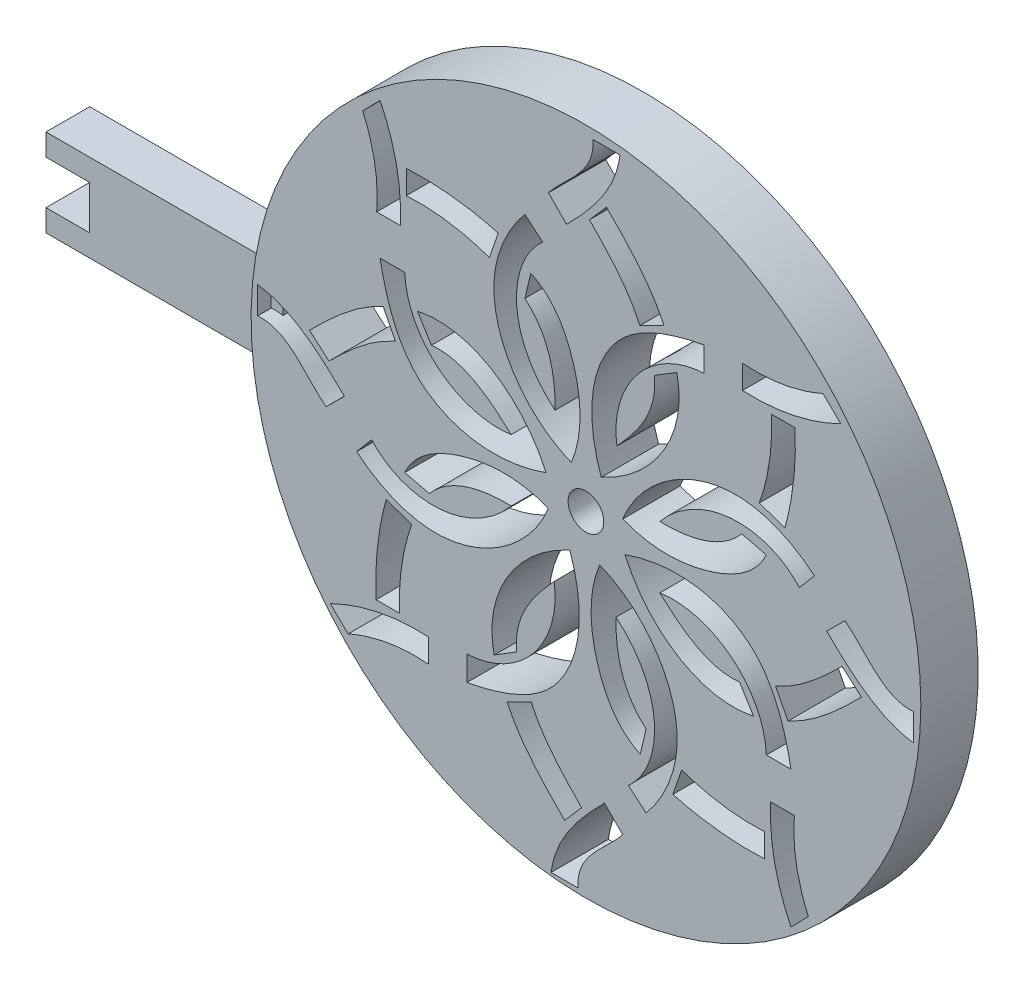
SolidWorks part; units mm, degrees
ref_plane "Front" through (0, 0, 0) normal (0, 0, 1) x (1, 0, 0)
ref_plane "Top" through (0, 0, 0) normal (0, 1, 0) x (1, 0, 0)
ref_plane "Right" through (0, 0, 0) normal (1, 0, 0) x (0, 0, -1)
sketch "Sketch4" plane through (0, 0, 0) normal (0, 0, 1) x (1, 0, 0)
  circle A0 centre (0, 0) radius 50
  dimension "D1" = 100
extrude "Boss-Extrude2" add sketch "Sketch4" along normal blind 6
sketch "Sketch1" plane through (0, 0, 0) normal (0, 0, 1) x (1, 0, 0)
  line L0 (0.5618, -51.3135) -> (0.5618, 17.3944) construction
  line L1 (-9.4536, -6.8886) -> (10.6305, 13.0689) construction
  line L2 (10.5773, -6.8886) -> (-9.5068, 13.0689) construction
  line L3 (16.331, 18.7335) -> (34.3707, 36.6595) construction
  line L4 (-9.5068, 13.0689) -> (-9.616, 13.1774) construction
  line L5 (6.3747, 16.0597) -> (8.2727, 17.2254)
  line L6 (10.5656, 20.3781) -> (10.5656, 18.3041)
  line L7 (0.9205, 24.6763) -> (2.3432, 26.3134)
  line L8 (5.1622, 19.0877) -> (7.1859, 20.1236)
  line L9 (4.5763, 24.9198) -> (5.8367, 23.184)
  line L11 (-12.0639, 21.0827) -> (-9.929, 21.0827)
  line L12 (-4.0159, 18.3041) -> (-4.513, 16.2283)
  line L13 (-4.513, 22.3493) -> (-3.0126, 21.0827)
  line L14 (-14.4893, 20.7159) -> (-14.4893, 18.7295)
  line L15 (-6.7607, 19.8672) -> (-7.5011, 17.7107)
  line L16 (-2.5302, 24.9198) -> (-1.0081, 23.3798)
  line L17 (1.2061, 30.6817) -> (3.4892, 30.6817)
  line L18 (-2.5302, 34.7098) -> (-0.6015, 34.7098)
  line L19 (-1.1362, 27.3587) -> (0.3144, 29.123)
  line L20 (13.7987, 20.6617) -> (13.7987, 18.6754)
  line L21 (20.5701, 21.8398) -> (22.067, 20.3781)
  line L22 (19.2048, 26.9759) -> (12.7252, 33.377)
  line L23 (17.8555, 25.6351) -> (12.2951, 31.1281)
  line L24 (12.7252, 33.377) -> (0.3144, 33.377)
  line L25 (0.3144, 33.377) -> (0.3144, 31.1281)
  line L26 (0.3144, 31.1281) -> (12.2951, 31.1281)
  line L27 (17.8555, 25.6351) -> (19.2048, 26.9759)
  line L28 (23.4061, 25.764) -> (14.5889, 34.4742)
  line L29 (14.5889, 34.4742) -> (17.3118, 40.6124)
  line L30 (15.254, 41.2328) -> (12.5727, 35.1885)
  line L31 (12.5727, 35.1885) -> (4.441, 35.1885)
  line L32 (4.441, 37.3216) -> (4.441, 35.1885)
  line L33 (4.441, 37.3216) -> (11.2937, 37.3216)
  line L34 (12.2009, 39.3665) -> (11.2937, 37.3216)
  line L35 (12.2009, 39.3665) -> (8.9373, 39.3665)
  line L36 (8.9373, 39.3665) -> (8.9373, 45.5487)
  line L37 (8.9373, 45.5487) -> (18.2458, 45.5487)
  line L38 (18.2458, 45.5487) -> (24.7099, 39.1361)
  line L39 (24.7099, 39.1361) -> (20.2368, 34.6271)
  line L40 (20.2368, 34.6271) -> (17.9282, 36.9173)
  line L41 (17.9282, 36.9173) -> (17.1172, 35.0891)
  line L42 (17.1172, 35.0891) -> (25.0916, 27.2115)
  line L43 (15.254, 41.2328) -> (11.0745, 41.2328)
  line L44 (11.0745, 41.2328) -> (11.0745, 43.6634)
  line L45 (11.0745, 43.6634) -> (17.6002, 43.6634)
  line L46 (17.6002, 43.6634) -> (21.9083, 39.2961)
  line L47 (21.9083, 39.2961) -> (20.2368, 37.6472)
  line L48 (20.2368, 37.6472) -> (17.3118, 40.6124)
  line L49 (20.5701, 27.611) -> (22.067, 26.3134)
  line L50 (16.4095, 21.4222) -> (18.768, 21.6675)
  line L51 (25.0916, 27.2115) -> (23.6255, 25.522)
  line L52 (23.6255, 25.522) -> (23.4061, 25.764)
  line L53 (26.0704, 37.6472) -> (21.7113, 33.377)
  line L54 (21.7113, 33.377) -> (24.0735, 30.9656)
  line L55 (24.0735, 30.9656) -> (22.8924, 29.8086)
  line L56 (22.8924, 29.8086) -> (24.3522, 28.3184)
  line L57 (24.3522, 28.3184) -> (26.9932, 30.9056)
  line L58 (26.9932, 30.9056) -> (24.7099, 33.2364)
  line L59 (24.7099, 33.2364) -> (26.2751, 34.7697)
  line L60 (26.2751, 34.7697) -> (32.3683, 28.6378)
  line L61 (32.3683, 28.6378) -> (30.7703, 27.0498)
  line L62 (30.7703, 27.0498) -> (28.3813, 29.454)
  line L63 (28.3813, 29.454) -> (23.1298, 24.2356)
  line L64 (23.1298, 24.2356) -> (24.575, 22.7369)
  line L65 (24.575, 22.7369) -> (28.5035, 26.525)
  line L66 (28.5035, 26.525) -> (30.5648, 24.3873)
  line L67 (30.5648, 24.3873) -> (35.1023, 28.7626)
  line L68 (35.1023, 28.7626) -> (26.0704, 37.6472)
  line L69 (-15.9935, 35.0891) -> (-20.9992, 30.1442)
  line L70 (-16.8045, 36.9173) -> (-15.9935, 35.0891)
  line L71 (-19.1132, 34.6271) -> (-16.8045, 36.9173)
  line L72 (-23.5862, 39.1361) -> (-19.1132, 34.6271)
  line L73 (-17.1221, 45.5487) -> (-23.5862, 39.1361)
  line L74 (-7.8136, 45.5487) -> (-17.1221, 45.5487)
  line L75 (-7.8136, 39.3665) -> (-7.8136, 45.5487)
  line L76 (-11.0772, 39.3665) -> (-7.8136, 39.3665)
  line L77 (-11.0772, 39.3665) -> (-10.17, 37.3216)
  line L78 (-3.3173, 37.3216) -> (-10.17, 37.3216)
  line L79 (-11.449, 35.1885) -> (-3.3173, 35.1885)
  line L80 (-14.1303, 41.2328) -> (-11.449, 35.1885)
  line L81 (-14.1303, 41.2328) -> (-9.9508, 41.2328)
  line L82 (-9.9508, 41.2328) -> (-9.9508, 43.6634)
  line L83 (-9.9508, 43.6634) -> (-16.4765, 43.6634)
  line L84 (-16.4765, 43.6634) -> (-20.7847, 39.2961)
  line L85 (-20.7847, 39.2961) -> (-19.1132, 37.6472)
  line L86 (-19.1132, 37.6472) -> (-16.1881, 40.6124)
  line L87 (-13.4652, 34.4742) -> (-16.1881, 40.6124)
  line L88 (-19.443, 28.5689) -> (-13.4652, 34.4742)
  line L89 (-19.443, 28.5689) -> (-20.9992, 30.1442)
  line L90 (-3.3173, 37.3216) -> (0.941, 37.3216)
  line L91 (0.941, 37.3216) -> (0.941, 35.0932)
  line L92 (0.941, 35.0932) -> (-3.3173, 35.1885)
  line L93 (-3.1732, 33.377) -> (-3.0126, 31.1281)
  line L94 (-3.0126, 31.1281) -> (-11.0772, 31.1281)
  line L95 (-11.0772, 31.1281) -> (-19.545, 22.5969)
  line L96 (-19.545, 22.5969) -> (-21.0309, 24.0717)
  line L97 (-21.0309, 24.0717) -> (-11.8349, 33.3366)
  line L98 (-11.8349, 33.3366) -> (-3.1732, 33.377)
  line L99 (1.441, 33.7567) -> (3.941, 33.7567)
  line L100 (3.941, 33.7567) -> (3.941, 39.3665)
  line L101 (3.941, 39.3665) -> (7.1859, 39.3665)
  line L102 (7.1859, 39.3665) -> (7.1859, 45.7803)
  line L103 (7.1859, 45.7803) -> (-5.8659, 45.7803)
  line L104 (-5.8659, 45.7803) -> (-5.8659, 39.3665)
  line L105 (-5.8659, 39.3665) -> (-2.5302, 39.3665)
  line L106 (-2.5302, 39.3665) -> (-2.5302, 37.8562)
  line L107 (-2.5302, 37.8562) -> (-0.6015, 37.8562)
  line L108 (-0.6015, 37.8562) -> (-0.6015, 41.6147)
  line L109 (-0.6015, 41.6147) -> (-3.5241, 41.6147)
  line L110 (-3.5241, 41.6147) -> (-3.5241, 43.6634)
  line L111 (-3.5241, 43.6634) -> (4.93, 43.6634)
  line L112 (4.93, 43.6634) -> (4.93, 41.6147)
  line L113 (4.93, 41.6147) -> (1.441, 41.6147)
  line L114 (1.441, 41.6147) -> (1.441, 33.7567)
  line L115 (39.1129, 2.2376) -> (31.255, 2.2376)
  line L116 (31.255, 2.2376) -> (31.255, -0.2624)
  line L117 (31.255, -0.2624) -> (36.8648, -0.2624)
  line L118 (36.8648, -0.2624) -> (36.8648, -3.5074)
  line L119 (36.8648, -3.5074) -> (43.2785, -3.5074)
  line L120 (43.2785, -3.5074) -> (43.2785, 9.5445)
  line L121 (43.2785, 9.5445) -> (36.8648, 9.5445)
  line L122 (36.8648, 9.5445) -> (36.8648, 6.2088)
  line L123 (36.8648, 6.2088) -> (35.3545, 6.2088)
  line L124 (35.3545, 6.2088) -> (35.3545, 4.28)
  line L125 (35.3545, 4.28) -> (39.1129, 4.28)
  line L126 (39.1129, 4.28) -> (39.1129, 7.2026)
  line L127 (39.1129, 7.2026) -> (41.1616, 7.2026)
  line L128 (41.1616, 7.2026) -> (41.1616, -1.2515)
  line L129 (41.1616, -1.2515) -> (39.1129, -1.2515)
  line L130 (39.1129, -1.2515) -> (39.1129, 2.2376)
  line L131 (23.0203, -19.9469) -> (23.2623, -19.7275)
  line L132 (23.2623, -19.7275) -> (31.9725, -10.9103)
  line L133 (31.9725, -10.9103) -> (38.1107, -13.6332)
  line L134 (35.1455, -16.5583) -> (38.1107, -13.6332)
  line L135 (36.7943, -18.2298) -> (35.1455, -16.5583)
  line L136 (41.1616, -13.9216) -> (36.7943, -18.2298)
  line L137 (41.1616, -7.3959) -> (41.1616, -13.9216)
  line L138 (38.731, -7.3959) -> (41.1616, -7.3959)
  line L139 (38.731, -11.5754) -> (38.731, -7.3959)
  line L140 (38.731, -11.5754) -> (32.6867, -8.8941)
  line L141 (32.6867, -8.8941) -> (32.6867, -0.7624)
  line L142 (34.8199, -0.7624) -> (32.6867, -0.7624)
  line L143 (34.8199, -0.7624) -> (34.8199, -7.6151)
  line L144 (36.8648, -8.5223) -> (34.8199, -7.6151)
  line L145 (36.8648, -8.5223) -> (36.8648, -5.2587)
  line L146 (36.8648, -5.2587) -> (43.047, -5.2587)
  line L147 (43.047, -5.2587) -> (43.047, -14.5672)
  line L148 (43.047, -14.5672) -> (36.6344, -21.0313)
  line L149 (36.6344, -21.0313) -> (32.1253, -16.5583)
  line L150 (32.1253, -16.5583) -> (34.4156, -14.2496)
  line L151 (34.4156, -14.2496) -> (32.5874, -13.4386)
  line L152 (32.5874, -13.4386) -> (24.7098, -21.413)
  line L153 (24.7098, -21.413) -> (23.0203, -19.9469)
  line L154 (26.2609, -31.4238) -> (35.1455, -22.3918)
  line L155 (35.1455, -22.3918) -> (30.8753, -18.0327)
  line L156 (30.8753, -18.0327) -> (28.4639, -20.395)
  line L157 (28.4639, -20.395) -> (27.3069, -19.2138)
  line L158 (27.3069, -19.2138) -> (25.8167, -20.6736)
  line L159 (25.8167, -20.6736) -> (28.4039, -23.3146)
  line L160 (28.4039, -23.3146) -> (30.7346, -21.0313)
  line L161 (30.7346, -21.0313) -> (32.2679, -22.5965)
  line L162 (32.2679, -22.5965) -> (26.1361, -28.6898)
  line L163 (26.1361, -28.6898) -> (24.5481, -27.0918)
  line L164 (24.5481, -27.0918) -> (26.9523, -24.7027)
  line L165 (26.9523, -24.7027) -> (21.7339, -19.4512)
  line L166 (21.7339, -19.4512) -> (20.2352, -20.8964)
  line L167 (20.2352, -20.8964) -> (24.0233, -24.8249)
  line L168 (24.0233, -24.8249) -> (21.8856, -26.8862)
  line L169 (21.8856, -26.8862) -> (26.2609, -31.4238)
  line L170 (32.5915, 2.7376) -> (32.6867, 6.9959)
  line L171 (32.6867, 15.1276) -> (32.6867, 6.9959)
  line L172 (38.731, 17.8089) -> (32.6867, 15.1276)
  line L173 (38.731, 17.8089) -> (38.731, 13.6294)
  line L174 (38.731, 13.6294) -> (41.1616, 13.6294)
  line L175 (41.1616, 13.6294) -> (41.1616, 20.1551)
  line L176 (41.1616, 20.1551) -> (36.7943, 24.4632)
  line L177 (36.7943, 24.4632) -> (35.1455, 22.7917)
  line L178 (35.1455, 22.7917) -> (38.1107, 19.8667)
  line L179 (31.9725, 17.1438) -> (38.1107, 19.8667)
  line L180 (26.0672, 23.1216) -> (31.9725, 17.1438)
  line L181 (26.0672, 23.1216) -> (27.6425, 24.6778)
  line L182 (32.5874, 19.6721) -> (27.6425, 24.6778)
  line L183 (34.4156, 20.4831) -> (32.5874, 19.6721)
  line L184 (32.1253, 22.7917) -> (34.4156, 20.4831)
  line L185 (36.6344, 27.2648) -> (32.1253, 22.7917)
  line L186 (43.047, 20.8007) -> (36.6344, 27.2648)
  line L187 (43.047, 11.4922) -> (43.047, 20.8007)
  line L188 (36.8648, 11.4922) -> (43.047, 11.4922)
  line L189 (36.8648, 14.7558) -> (36.8648, 11.4922)
  line L190 (36.8648, 14.7558) -> (34.8199, 13.8486)
  line L191 (34.8199, 6.9959) -> (34.8199, 13.8486)
  line L192 (34.8199, 6.9959) -> (34.8199, 2.7376)
  line L193 (34.8199, 2.7376) -> (32.5915, 2.7376)
  line L194 (23.1334, -14.177) -> (24.4742, -15.5263)
  line L195 (24.4742, -15.5263) -> (30.8753, -9.0466)
  line L196 (30.8753, -9.0466) -> (30.8753, 3.3641)
  line L197 (30.8753, 3.3641) -> (28.6264, 3.3641)
  line L198 (28.6264, 3.3641) -> (28.6264, -8.6165)
  line L199 (23.1334, -14.177) -> (28.6264, -8.6165)
  line L200 (30.8348, 15.5135) -> (30.8753, 6.8518)
  line L201 (30.8753, 6.8518) -> (28.6264, 6.6912)
  line L202 (28.6264, 6.6912) -> (28.6264, 14.7558)
  line L203 (28.6264, 14.7558) -> (20.0952, 23.2236)
  line L204 (20.0952, 23.2236) -> (21.57, 24.7094)
  line L205 (21.57, 24.7094) -> (30.8348, 15.5135)
  line L206 (18.9205, -12.7309) -> (19.1658, -15.0894)
  line L207 (25.1092, -16.8915) -> (23.8117, -18.3884)
  line L208 (24.857, 4.8148) -> (26.6212, 3.3641)
  line L209 (32.2081, 6.2088) -> (32.2081, 4.28)
  line L210 (28.18, 2.4725) -> (28.18, 0.1894)
  line L211 (22.4181, 6.2088) -> (20.8781, 4.6867)
  line L212 (22.4181, -0.8977) -> (20.6823, -2.1581)
  line L213 (16.586, -1.4836) -> (17.6218, -3.5074)
  line L214 (22.1746, 2.7581) -> (23.8117, 1.3354)
  line L215 (19.3381, -16.8915) -> (17.8764, -18.3884)
  line L216 (18.16, -10.1201) -> (16.1736, -10.1201)
  line L217 (17.3654, 10.4393) -> (15.209, 11.1797)
  line L218 (18.2141, 18.1679) -> (16.2278, 18.1679)
  line L219 (19.8476, 8.1916) -> (18.581, 6.6912)
  line L220 (15.8023, 7.6945) -> (13.7266, 8.1916)
  line L221 (17.8764, -6.887) -> (15.8023, -6.887)
  line L222 (13.558, -2.6961) -> (14.7236, -4.5941)
  line L223 (20.0952, 1.5374) -> (18.581, 0.1894)
  line L224 (18.581, 15.7425) -> (18.581, 13.6075)
  line L225 (-0.2642, -35.4343) -> (-0.2642, -27.5764)
  line L226 (-0.2642, -27.5764) -> (-2.7642, -27.5764)
  line L227 (-2.7642, -27.5764) -> (-2.7642, -33.1862)
  line L228 (-2.7642, -33.1862) -> (-6.0091, -33.1862)
  line L229 (-6.0091, -33.1862) -> (-6.0091, -39.6)
  line L230 (-6.0091, -39.6) -> (7.0427, -39.6)
  line L231 (7.0427, -39.6) -> (7.0427, -33.1862)
  line L232 (7.0427, -33.1862) -> (3.707, -33.1862)
  line L233 (3.707, -33.1862) -> (3.707, -31.6759)
  line L234 (3.707, -31.6759) -> (1.7783, -31.6759)
  line L235 (1.7783, -31.6759) -> (1.7783, -35.4343)
  line L236 (1.7783, -35.4343) -> (4.7009, -35.4343)
  line L237 (4.7009, -35.4343) -> (4.7009, -37.4831)
  line L238 (4.7009, -37.4831) -> (-3.7532, -37.4831)
  line L239 (-3.7532, -37.4831) -> (-3.7532, -35.4343)
  line L240 (-3.7532, -35.4343) -> (-0.2642, -35.4343)
  line L241 (-22.4487, -19.3417) -> (-22.2292, -19.5837)
  line L242 (-22.2292, -19.5837) -> (-13.412, -28.2939)
  line L243 (-13.412, -28.2939) -> (-16.135, -34.4321)
  line L244 (-19.06, -31.4669) -> (-16.135, -34.4321)
  line L245 (-20.7315, -33.1158) -> (-19.06, -31.4669)
  line L246 (-16.4233, -37.4831) -> (-20.7315, -33.1158)
  line L247 (-9.8976, -37.4831) -> (-16.4233, -37.4831)
  line L248 (-9.8976, -35.0525) -> (-9.8976, -37.4831)
  line L249 (-14.0771, -35.0525) -> (-9.8976, -35.0525)
  line L250 (-14.0771, -35.0525) -> (-11.3959, -29.0082)
  line L251 (-11.3959, -29.0082) -> (-3.2642, -29.0082)
  line L252 (-3.2642, -31.1413) -> (-3.2642, -29.0082)
  line L253 (-3.2642, -31.1413) -> (-10.1169, -31.1413)
  line L254 (-11.024, -33.1862) -> (-10.1169, -31.1413)
  line L255 (-11.024, -33.1862) -> (-7.7604, -33.1862)
  line L256 (-7.7604, -33.1862) -> (-7.7604, -39.3684)
  line L257 (-7.7604, -39.3684) -> (-17.0689, -39.3684)
  line L258 (-17.0689, -39.3684) -> (-23.5331, -32.9558)
  line L259 (-23.5331, -32.9558) -> (-19.06, -28.4468)
  line L260 (-19.06, -28.4468) -> (-16.7514, -30.737)
  line L261 (-16.7514, -30.737) -> (-15.9404, -28.9088)
  line L262 (-15.9404, -28.9088) -> (-23.9147, -21.0312)
  line L263 (-23.9147, -21.0312) -> (-22.4487, -19.3417)
  line L264 (-33.9255, -22.5823) -> (-24.8935, -31.4669)
  line L265 (-24.8935, -31.4669) -> (-20.5345, -27.1967)
  line L266 (-20.5345, -27.1967) -> (-22.8967, -24.7853)
  line L267 (-22.8967, -24.7853) -> (-21.7156, -23.6283)
  line L268 (-21.7156, -23.6283) -> (-23.1754, -22.1381)
  line L269 (-23.1754, -22.1381) -> (-25.8163, -24.7253)
  line L270 (-25.8163, -24.7253) -> (-23.5331, -27.0561)
  line L271 (-23.5331, -27.0561) -> (-25.0983, -28.5894)
  line L272 (-25.0983, -28.5894) -> (-31.1915, -22.4575)
  line L273 (-31.1915, -22.4575) -> (-29.5935, -20.8695)
  line L274 (-29.5935, -20.8695) -> (-27.2044, -23.2737)
  line L275 (-27.2044, -23.2737) -> (-21.9529, -18.0553)
  line L276 (-21.9529, -18.0553) -> (-23.3981, -16.5566)
  line L277 (-23.3981, -16.5566) -> (-27.3267, -20.3447)
  line L278 (-27.3267, -20.3447) -> (-29.388, -18.207)
  line L279 (-29.388, -18.207) -> (-33.9255, -22.5823)
  line L280 (0.2358, -28.9129) -> (4.4942, -29.0082)
  line L281 (12.6259, -29.0082) -> (4.4942, -29.0082)
  line L282 (15.3072, -35.0525) -> (12.6259, -29.0082)
  line L283 (15.3072, -35.0525) -> (11.1277, -35.0525)
  line L284 (11.1277, -35.0525) -> (11.1277, -37.4831)
  line L285 (11.1277, -37.4831) -> (17.6534, -37.4831)
  line L286 (17.6534, -37.4831) -> (21.9615, -33.1158)
  line L287 (21.9615, -33.1158) -> (20.29, -31.4669)
  line L288 (20.29, -31.4669) -> (17.365, -34.4321)
  line L289 (14.6421, -28.2939) -> (17.365, -34.4321)
  line L290 (20.6199, -22.3886) -> (14.6421, -28.2939)
  line L291 (20.6199, -22.3886) -> (22.176, -23.9639)
  line L292 (17.1704, -28.9088) -> (22.176, -23.9639)
  line L293 (17.9814, -30.737) -> (17.1704, -28.9088)
  line L294 (20.29, -28.4468) -> (17.9814, -30.737)
  line L295 (24.7631, -32.9558) -> (20.29, -28.4468)
  line L296 (18.2989, -39.3684) -> (24.7631, -32.9558)
  line L297 (8.9905, -39.3684) -> (18.2989, -39.3684)
  line L298 (8.9905, -33.1862) -> (8.9905, -39.3684)
  line L299 (12.2541, -33.1862) -> (8.9905, -33.1862)
  line L300 (12.2541, -33.1862) -> (11.3469, -31.1413)
  line L301 (4.4942, -31.1413) -> (11.3469, -31.1413)
  line L302 (4.4942, -31.1413) -> (0.2358, -31.1413)
  line L303 (0.2358, -31.1413) -> (0.2358, -28.9129)
  line L304 (-16.6787, -19.4548) -> (-18.028, -20.7956)
  line L305 (-18.028, -20.7956) -> (-11.5483, -27.1967)
  line L306 (-11.5483, -27.1967) -> (0.8624, -27.1967)
  line L307 (0.8624, -27.1967) -> (0.8624, -24.9478)
  line L308 (0.8624, -24.9478) -> (-11.1183, -24.9478)
  line L309 (-16.6787, -19.4548) -> (-11.1183, -24.9478)
  line L310 (13.0117, -27.1563) -> (4.3501, -27.1967)
  line L311 (4.3501, -27.1967) -> (4.1895, -24.9478)
  line L312 (4.1895, -24.9478) -> (12.2541, -24.9478)
  line L313 (12.2541, -24.9478) -> (20.7219, -16.4166)
  line L314 (20.7219, -16.4166) -> (22.2077, -17.8914)
  line L315 (22.2077, -17.8914) -> (13.0117, -27.1563)
  line L316 (-15.2326, -15.2419) -> (-17.5912, -15.4872)
  line L317 (-19.3933, -21.4307) -> (-20.8901, -20.1331)
  line L318 (2.313, -21.1784) -> (0.8624, -22.9427)
  line L319 (3.707, -28.5295) -> (1.7783, -28.5295)
  line L320 (-0.0293, -24.5014) -> (-2.3123, -24.5014)
  line L321 (3.707, -18.7395) -> (2.1849, -17.1995)
  line L322 (-3.3995, -18.7395) -> (-4.6598, -17.0037)
  line L323 (-3.9854, -12.9074) -> (-6.0091, -13.9433)
  line L324 (0.2564, -18.496) -> (-1.1663, -20.1331)
  line L325 (-19.3933, -15.6595) -> (-20.8901, -14.1978)
  line L326 (-12.6218, -14.4814) -> (-12.6218, -12.4951)
  line L327 (7.9376, -13.6868) -> (8.6779, -11.5304)
  line L328 (15.6662, -14.5355) -> (15.6662, -12.5492)
  line L329 (5.6899, -16.169) -> (4.1895, -14.9024)
  line L330 (5.1928, -12.1238) -> (5.6899, -10.048)
  line L331 (-9.3887, -14.1978) -> (-9.3887, -12.1238)
  line L332 (-5.1978, -9.8794) -> (-7.0958, -11.0451)
  line L333 (-0.9643, -16.4166) -> (-2.3123, -14.9024)
  line L334 (13.2408, -14.9024) -> (11.1058, -14.9024)
  line L335 (-37.9361, 3.9427) -> (-30.0781, 3.9427)
  line L336 (-30.0781, 3.9427) -> (-30.0781, 6.4427)
  line L337 (-30.0781, 6.4427) -> (-35.688, 6.4427)
  line L338 (-35.688, 6.4427) -> (-35.688, 9.6877)
  line L339 (-35.688, 9.6877) -> (-42.1017, 9.6877)
  line L340 (-42.1017, 9.6877) -> (-42.1017, -3.3642)
  line L341 (-42.1017, -3.3642) -> (-35.688, -3.3642)
  line L342 (-35.688, -3.3642) -> (-35.688, -0.0285)
  line L343 (-35.688, -0.0285) -> (-34.1776, -0.0285)
  line L344 (-34.1776, -0.0285) -> (-34.1776, 1.9003)
  line L345 (-34.1776, 1.9003) -> (-37.9361, 1.9003)
  line L346 (-37.9361, 1.9003) -> (-37.9361, -1.0223)
  line L347 (-37.9361, -1.0223) -> (-39.9848, -1.0223)
  line L348 (-39.9848, -1.0223) -> (-39.9848, 7.4318)
  line L349 (-39.9848, 7.4318) -> (-37.9361, 7.4318)
  line L350 (-37.9361, 7.4318) -> (-37.9361, 3.9427)
  line L351 (-21.8435, 26.1272) -> (-22.0854, 25.9078)
  line L352 (-22.0854, 25.9078) -> (-30.7956, 17.0906)
  line L353 (-30.7956, 17.0906) -> (-36.9338, 19.8135)
  line L354 (-33.9686, 22.7386) -> (-36.9338, 19.8135)
  line L355 (-35.6175, 24.4101) -> (-33.9686, 22.7386)
  line L356 (-39.9848, 20.1019) -> (-35.6175, 24.4101)
  line L357 (-39.9848, 13.5762) -> (-39.9848, 20.1019)
  line L358 (-37.5542, 13.5762) -> (-39.9848, 13.5762)
  line L359 (-37.5542, 17.7557) -> (-37.5542, 13.5762)
  line L360 (-37.5542, 17.7557) -> (-31.5099, 15.0744)
  line L361 (-31.5099, 15.0744) -> (-31.5099, 6.9427)
  line L362 (-33.643, 6.9427) -> (-31.5099, 6.9427)
  line L363 (-33.643, 6.9427) -> (-33.643, 13.7954)
  line L364 (-35.688, 14.7026) -> (-33.643, 13.7954)
  line L365 (-35.688, 14.7026) -> (-35.688, 11.439)
  line L366 (-35.688, 11.439) -> (-41.8701, 11.439)
  line L367 (-41.8701, 11.439) -> (-41.8701, 20.7475)
  line L368 (-41.8701, 20.7475) -> (-35.4575, 27.2116)
  line L369 (-35.4575, 27.2116) -> (-30.9485, 22.7386)
  line L370 (-30.9485, 22.7386) -> (-33.2387, 20.4299)
  line L371 (-33.2387, 20.4299) -> (-31.4105, 19.6189)
  line L372 (-31.4105, 19.6189) -> (-23.5329, 27.5933)
  line L373 (-23.5329, 27.5933) -> (-21.8435, 26.1272)
  line L374 (-25.084, 37.6041) -> (-33.9686, 28.5721)
  line L375 (-33.9686, 28.5721) -> (-29.6984, 24.213)
  line L376 (-29.6984, 24.213) -> (-27.2871, 26.5753)
  line L377 (-27.2871, 26.5753) -> (-26.13, 25.3941)
  line L378 (-26.13, 25.3941) -> (-24.6399, 26.8539)
  line L379 (-24.6399, 26.8539) -> (-27.227, 29.4949)
  line L380 (-27.227, 29.4949) -> (-29.5578, 27.2116)
  line L381 (-29.5578, 27.2116) -> (-31.0911, 28.7768)
  line L382 (-31.0911, 28.7768) -> (-24.9592, 34.8701)
  line L383 (-24.9592, 34.8701) -> (-23.3713, 33.2721)
  line L384 (-23.3713, 33.2721) -> (-25.7755, 30.883)
  line L385 (-25.7755, 30.883) -> (-20.5571, 25.6315)
  line L386 (-20.5571, 25.6315) -> (-19.0583, 27.0767)
  line L387 (-19.0583, 27.0767) -> (-22.8464, 31.0053)
  line L388 (-22.8464, 31.0053) -> (-20.7087, 33.0665)
  line L389 (-20.7087, 33.0665) -> (-25.084, 37.6041)
  line L390 (-31.4146, 3.4427) -> (-31.5099, -0.8156)
  line L391 (-31.5099, -8.9473) -> (-31.5099, -0.8156)
  line L392 (-37.5542, -11.6286) -> (-31.5099, -8.9473)
  line L393 (-37.5542, -11.6286) -> (-37.5542, -7.4491)
  line L394 (-37.5542, -7.4491) -> (-39.9848, -7.4491)
  line L395 (-39.9848, -7.4491) -> (-39.9848, -13.9748)
  line L396 (-39.9848, -13.9748) -> (-35.6175, -18.2829)
  line L397 (-35.6175, -18.2829) -> (-33.9686, -16.6114)
  line L398 (-33.9686, -16.6114) -> (-36.9338, -13.6864)
  line L399 (-30.7956, -10.9635) -> (-36.9338, -13.6864)
  line L400 (-24.8903, -16.9413) -> (-30.7956, -10.9635)
  line L401 (-24.8903, -16.9413) -> (-26.4656, -18.4975)
  line L402 (-31.4105, -13.4918) -> (-26.4656, -18.4975)
  line L403 (-33.2387, -14.3028) -> (-31.4105, -13.4918)
  line L404 (-30.9485, -16.6114) -> (-33.2387, -14.3028)
  line L405 (-35.4575, -21.0845) -> (-30.9485, -16.6114)
  line L406 (-41.8701, -14.6204) -> (-35.4575, -21.0845)
  line L407 (-41.8701, -5.3119) -> (-41.8701, -14.6204)
  line L408 (-35.688, -5.3119) -> (-41.8701, -5.3119)
  line L409 (-35.688, -8.5755) -> (-35.688, -5.3119)
  line L410 (-35.688, -8.5755) -> (-33.643, -7.6683)
  line L411 (-33.643, -0.8156) -> (-33.643, -7.6683)
  line L412 (-33.643, -0.8156) -> (-33.643, 3.4427)
  line L413 (-33.643, 3.4427) -> (-31.4146, 3.4427)
  line L414 (-21.9566, 20.3573) -> (-23.2973, 21.7066)
  line L415 (-23.2973, 21.7066) -> (-29.6984, 15.2269)
  line L416 (-29.6984, 15.2269) -> (-29.6984, 2.8162)
  line L417 (-29.6984, 2.8162) -> (-27.4496, 2.8162)
  line L418 (-27.4496, 2.8162) -> (-27.4496, 14.7968)
  line L419 (-21.9566, 20.3573) -> (-27.4496, 14.7968)
  line L420 (-29.658, -9.3332) -> (-29.6984, -0.6715)
  line L421 (-29.6984, -0.6715) -> (-27.4496, -0.5109)
  line L422 (-27.4496, -0.5109) -> (-27.4496, -8.5755)
  line L423 (-27.4496, -8.5755) -> (-18.9184, -17.0433)
  line L424 (-18.9184, -17.0433) -> (-20.3932, -18.5291)
  line L425 (-20.3932, -18.5291) -> (-29.658, -9.3332)
  line L426 (-17.7436, 18.9112) -> (-17.9889, 21.2697)
  line L427 (-23.9324, 23.0718) -> (-22.6348, 24.5687)
  line L428 (-23.6801, 1.3655) -> (-25.4444, 2.8162)
  line L429 (-31.0312, -0.0285) -> (-31.0312, 1.9003)
  line L430 (-27.0032, 3.7078) -> (-27.0032, 5.9909)
  line L431 (-21.2412, -0.0285) -> (-19.7012, 1.4936)
  line L432 (-21.2412, 7.078) -> (-19.5054, 8.3384)
  line L433 (-15.4092, 7.6639) -> (-16.445, 9.6877)
  line L434 (-20.9977, 3.4222) -> (-22.6348, 4.8449)
  line L435 (-18.1612, 23.0718) -> (-16.6995, 24.5687)
  line L436 (-16.9831, 16.3004) -> (-14.9968, 16.3004)
  line L437 (-16.1886, -4.259) -> (-14.0322, -4.9994)
  line L438 (-17.0373, -11.9876) -> (-15.051, -11.9876)
  line L439 (-18.6707, -2.0113) -> (-17.4041, -0.5109)
  line L440 (-14.6255, -1.5142) -> (-12.5497, -2.0113)
  line L441 (-16.6995, 13.0673) -> (-14.6255, 13.0673)
  line L442 (-12.3811, 8.8764) -> (-13.5468, 10.7744)
  line L443 (-18.9184, 4.6429) -> (-17.4041, 5.9909)
  line L444 (-17.4041, -9.5622) -> (-17.4041, -7.4272)
  line L445 (-15.0302, 18.5575) -> (-34.8365, 38.2389) construction
  line L446 (0.5618, 25.0422) -> (0.5618, 52.6865) construction
  spline S0 degree 3 poles (1.9128, 6.4081) (5.9565, 8.1949) (9.2924, 12.4957) (8.2727, 17.2254) knots 0 0 0 0 1 1 1 1
  spline S1 degree 3 poles (1.9128, 6.4081) (1.0549, 8.7838) (0.6747, 12.8499) (3.9435, 18.6992) (8.1058, 19.9135) (10.5656, 20.3781) knots 0 0 0 0 0.397628 0.593751 1 1 1 1
  spline S2 degree 3 poles (10.5656, 18.3041) (8.5021, 18.2289) (4.3462, 16.0974) (2.887, 11.6127) (3.2274, 9.3434) knots 0 0 0 0 0.475044 1 1 1 1
  spline S3 degree 3 poles (3.2274, 9.3434) (4.909, 11.1573) (6.6886, 13.3688) (6.3747, 16.0597) knots 0 0 0 0 1 1 1 1
  spline S8 degree 3 poles (7.1859, 20.1236) (6.0615, 22.5345) (4.2017, 24.4648) (2.3432, 26.3134) knots 0 0 0 0 1 1 1 1
  spline S9 degree 3 poles (5.1622, 19.0877) (4.204, 21.2611) (2.5611, 23.0083) (0.9205, 24.6763) knots 0 0 0 0 1 1 1 1
  spline S16 degree 3 poles (-0.6015, 6.2318) (0.3774, 8.5914) (0.2368, 13.2339) (-2.0951, 17.4295) (-4.0159, 18.3041) knots 0 0 0 0 0.551732 1 1 1 1
  spline S17 degree 3 poles (-4.513, 16.2283) (-2.5157, 14.566) (-1.8872, 11.8216) (-1.9798, 9.3434) knots 0 0 0 0 1 1 1 1
  spline S18 degree 3 poles (-1.9798, 9.3434) (-3.3571, 10.4816) (-6.0015, 14.3076) (-5.1059, 19.2239) (-3.0126, 21.0827) knots 0 0 0 0 0.406587 1 1 1 1
  spline S19 degree 3 poles (-4.513, 22.3493) (-5.9818, 20.6238) (-8.8778, 14.3072) (-4.4607, 7.7513) (-0.6015, 6.2318) knots 0 0 0 0 0.358842 1 1 1 1
  spline S20 degree 2 poles (-14.4893, 20.7159) (-10.5651, 20.9108) (-6.7607, 19.8672) knots 0 0 0 1 1 1
  spline S21 degree 2 poles (-14.4893, 18.7295) (-10.9112, 18.9185) (-7.5011, 17.7107) knots 0 0 0 1 1 1
  spline S22 degree 3 poles (-1.0081, 23.3798) (0.9762, 25.3708) (3.1191, 27.7529) (3.4892, 30.6817) knots 0 0 0 0 1 1 1 1
  spline S23 degree 3 poles (1.2061, 30.6817) (1.4387, 28.1115) (-1.2075, 26.6689) (-2.5302, 24.9198) knots 0 0 0 0 1 1 1 1
  spline S24 degree 2 poles (-0.6015, 34.7098) (-1.0842, 31.7413) (0.3144, 29.123) knots 0 0 0 1 1 1
  spline S25 degree 2 poles (-2.5302, 34.7098) (-3.2008, 30.7791) (-1.1362, 27.3587) knots 0 0 0 1 1 1
  spline S26 degree 2 poles (13.7987, 20.6617) (17.3177, 20.3883) (20.5701, 21.8398) knots 0 0 0 1 1 1
  spline S27 degree 2 poles (13.7987, 18.6754) (18.1381, 18.4571) (22.067, 20.3781) knots 0 0 0 1 1 1
  spline S28 degree 3 poles (16.4095, 21.4222) (16.749, 24.0357) (18.841, 25.8563) (20.5701, 27.611) knots 0 0 0 0 1 1 1 1
  spline S29 degree 3 poles (18.768, 21.6675) (18.7945, 23.757) (20.731, 24.9709) (22.067, 26.3134) knots 0 0 0 0 1 1 1 1
  spline S32 degree 2 poles (15.4515, 15.8331) (15.4515, 14.9513) (15.4515, 14.0695) knots 0 0 0 1 1 1
  spline S33 degree 3 poles (19.1658, -15.0894) (21.2553, -15.1159) (22.4692, -17.0524) (23.8117, -18.3884) knots 0 0 0 0 1 1 1 1
  spline S34 degree 3 poles (18.9205, -12.7309) (21.534, -13.0704) (23.3546, -15.1625) (25.1092, -16.8915) knots 0 0 0 0 1 1 1 1
  spline S35 degree 2 poles (32.2081, 4.28) (29.2396, 4.7628) (26.6212, 3.3641) knots 0 0 0 1 1 1
  spline S36 degree 2 poles (32.2081, 6.2088) (28.2774, 6.8794) (24.857, 4.8148) knots 0 0 0 1 1 1
  spline S37 degree 3 poles (20.8781, 4.6867) (22.8691, 2.7024) (25.2512, 0.5595) (28.18, 0.1894) knots 0 0 0 0 1 1 1 1
  spline S38 degree 3 poles (28.18, 2.4725) (25.6097, 2.2399) (24.1672, 4.8861) (22.4181, 6.2088) knots 0 0 0 0 1 1 1 1
  spline S39 degree 2 poles (13.3314, -11.7729) (12.4496, -11.7729) (11.5678, -11.7729) knots 0 0 0 1 1 1
  spline S42 degree 2 poles (20.6823, -2.1581) (22.3603, -3.9755) (23.2727, -6.3014) knots 0 0 0 1 1 1
  spline S43 degree 3 poles (22.4181, -0.8977) (24.215, -2.6753) (24.9751, -5.1383) (25.9383, -7.3959) knots 0 0 0 0 1 1 1 1
  spline S46 degree 3 poles (17.6218, -3.5074) (20.0327, -2.3829) (21.9631, -0.5231) (23.8117, 1.3354) knots 0 0 0 0 1 1 1 1
  spline S47 degree 3 poles (16.586, -1.4836) (18.7594, -0.5255) (20.5066, 1.1175) (22.1746, 2.7581) knots 0 0 0 0 1 1 1 1
  spline S48 degree 2 poles (16.1736, -10.1201) (15.9553, -14.4595) (17.8764, -18.3884) knots 0 0 0 1 1 1
  spline S49 degree 2 poles (18.16, -10.1201) (17.8866, -13.6391) (19.3381, -16.8915) knots 0 0 0 1 1 1
  spline S50 degree 2 poles (16.2278, 18.1679) (16.4168, 14.5898) (15.209, 11.1797) knots 0 0 0 1 1 1
  spline S51 degree 2 poles (18.2141, 18.1679) (18.4091, 14.2437) (17.3654, 10.4393) knots 0 0 0 1 1 1
  spline S52 degree 3 poles (6.8417, 5.6584) (7.9799, 7.0357) (11.8059, 9.6801) (16.7222, 8.7845) (18.581, 6.6912) knots 0 0 0 0 0.406587 1 1 1 1
  spline S53 degree 3 poles (13.7266, 8.1916) (12.0643, 6.1943) (9.3199, 5.5658) (6.8417, 5.6584) knots 0 0 0 0 1 1 1 1
  spline S54 degree 3 poles (3.7301, 4.28) (6.0897, 3.3012) (10.7321, 3.4417) (14.9278, 5.7737) (15.8023, 7.6945) knots 0 0 0 0 0.551732 1 1 1 1
  spline S55 degree 3 poles (19.8476, 8.1916) (18.1221, 9.6604) (11.8055, 12.5564) (5.2495, 8.1393) (3.7301, 4.28) knots 0 0 0 0 0.358842 1 1 1 1
  spline S56 degree 3 poles (15.8023, -6.887) (15.7272, -4.8235) (13.5956, -0.6677) (9.111, 0.7916) (6.8417, 0.4512) knots 0 0 0 0 0.475044 1 1 1 1
  spline S57 degree 3 poles (6.8417, 0.4512) (8.6556, -1.2305) (10.8671, -3.0101) (13.558, -2.6961) knots 0 0 0 0 1 1 1 1
  spline S58 degree 3 poles (3.9064, 1.7658) (5.6932, -2.2779) (9.9939, -5.6138) (14.7236, -4.5941) knots 0 0 0 0 1 1 1 1
  spline S59 degree 3 poles (3.9064, 1.7658) (6.2821, 2.6237) (10.3482, 3.0039) (16.1975, -0.2649) (17.4118, -4.4272) (17.8764, -6.887) knots 0 0 0 0 0.397628 0.593751 1 1 1 1
  spline S66 degree 3 poles (-17.5912, -15.4872) (-17.6177, -17.5767) (-19.5542, -18.7906) (-20.8901, -20.1331) knots 0 0 0 0 1 1 1 1
  spline S67 degree 3 poles (-15.2326, -15.2419) (-15.5721, -17.8554) (-17.6642, -19.676) (-19.3933, -21.4307) knots 0 0 0 0 1 1 1 1
  spline S68 degree 2 poles (1.7783, -28.5295) (2.2611, -25.561) (0.8624, -22.9427) knots 0 0 0 1 1 1
  spline S69 degree 2 poles (3.707, -28.5295) (4.3777, -24.5988) (2.313, -21.1784) knots 0 0 0 1 1 1
  spline S70 degree 3 poles (2.1849, -17.1995) (0.2007, -19.1905) (-1.9422, -21.5726) (-2.3123, -24.5014) knots 0 0 0 0 1 1 1 1
  spline S71 degree 3 poles (-0.0293, -24.5014) (-0.2619, -21.9312) (2.3843, -20.4886) (3.707, -18.7395) knots 0 0 0 0 1 1 1 1
  spline S75 degree 2 poles (-4.6598, -17.0037) (-6.4772, -18.6818) (-8.8031, -19.5941) knots 0 0 0 1 1 1
  spline S76 degree 3 poles (-3.3995, -18.7395) (-5.177, -20.5365) (-7.64, -21.2965) (-9.8976, -22.2597) knots 0 0 0 0 1 1 1 1
  spline S79 degree 3 poles (-6.0091, -13.9433) (-4.8847, -16.3542) (-3.0248, -18.2845) (-1.1663, -20.1331) knots 0 0 0 0 1 1 1 1
  spline S80 degree 3 poles (-3.9854, -12.9074) (-3.0272, -15.0808) (-1.3842, -16.828) (0.2564, -18.496) knots 0 0 0 0 1 1 1 1
  spline S81 degree 2 poles (-12.6218, -12.4951) (-16.9612, -12.2768) (-20.8901, -14.1978) knots 0 0 0 1 1 1
  spline S82 degree 2 poles (-12.6218, -14.4814) (-16.1408, -14.208) (-19.3933, -15.6595) knots 0 0 0 1 1 1
  spline S83 degree 2 poles (15.6662, -12.5492) (12.0881, -12.7382) (8.6779, -11.5304) knots 0 0 0 1 1 1
  spline S84 degree 2 poles (15.6662, -14.5355) (11.742, -14.7305) (7.9376, -13.6868) knots 0 0 0 1 1 1
  spline S85 degree 3 poles (3.1567, -3.1631) (4.5339, -4.3013) (7.1784, -8.1273) (6.2827, -13.0436) (4.1895, -14.9024) knots 0 0 0 0 0.406587 1 1 1 1
  spline S86 degree 3 poles (5.6899, -10.048) (3.6926, -8.3857) (3.0641, -5.6413) (3.1567, -3.1631) knots 0 0 0 0 1 1 1 1
  spline S87 degree 3 poles (1.7783, -0.0515) (0.7995, -2.4111) (0.94, -7.0536) (3.2719, -11.2492) (5.1928, -12.1238) knots 0 0 0 0 0.551732 1 1 1 1
  spline S88 degree 3 poles (5.6899, -16.169) (7.1586, -14.4435) (10.0547, -8.1269) (5.6376, -1.5709) (1.7783, -0.0515) knots 0 0 0 0 0.358842 1 1 1 1
  spline S89 degree 3 poles (-9.3887, -12.1238) (-7.3253, -12.0486) (-3.1694, -9.9171) (-1.7102, -5.4324) (-2.0506, -3.1631) knots 0 0 0 0 0.475044 1 1 1 1
  spline S90 degree 3 poles (-2.0506, -3.1631) (-3.7322, -4.977) (-5.5118, -7.1885) (-5.1978, -9.8794) knots 0 0 0 0 1 1 1 1
  spline S91 degree 3 poles (-0.7359, -0.2278) (-4.7797, -2.0146) (-8.1155, -6.3154) (-7.0958, -11.0451) knots 0 0 0 0 1 1 1 1
  spline S92 degree 3 poles (-0.7359, -0.2278) (0.1219, -2.6035) (0.5022, -6.6696) (-2.7667, -12.5189) (-6.9289, -13.7332) (-9.3887, -14.1978) knots 0 0 0 0 0.397628 0.593751 1 1 1 1
  spline S93 degree 2 poles (-2.3123, -14.9024) (-0.4956, -13.3408) (0.615, -11.2141) knots 0 0 0 1 1 1
  spline S94 degree 2 poles (-0.9643, -16.4166) (0.1091, -15.7905) (0.615, -14.656) knots 0 0 0 1 1 1
  spline S95 degree 3 poles (9.7099, -19.5941) (7.9048, -18.6568) (4.4805, -16.2603) (1.5551, -13.1689) (0.615, -11.2141) knots 0 0 0 0 0.484948 1 1 1 1
  spline S96 degree 3 poles (0.615, -14.656) (2.991, -18.2827) (7.1504, -20.395) (10.88, -22.2597) knots 0 0 0 0 1 1 1 1
  spline S97 degree 2 poles (13.2408, -14.9024) (12.9451, -18.8502) (10.88, -22.2597) knots 0 0 0 1 1 1
  spline S98 degree 2 poles (11.1058, -14.9024) (11.0566, -17.4563) (9.7099, -19.5941) knots 0 0 0 1 1 1
  spline S99 degree 3 poles (-17.9889, 21.2697) (-20.0784, 21.2962) (-21.2923, 23.2327) (-22.6348, 24.5687) knots 0 0 0 0 1 1 1 1
  spline S100 degree 3 poles (-17.7436, 18.9112) (-20.3571, 19.2507) (-22.1778, 21.3428) (-23.9324, 23.0718) knots 0 0 0 0 1 1 1 1
  spline S101 degree 2 poles (-31.0312, 1.9003) (-28.0628, 1.4175) (-25.4444, 2.8162) knots 0 0 0 1 1 1
  spline S102 degree 2 poles (-31.0312, -0.0285) (-27.1005, -0.6991) (-23.6801, 1.3655) knots 0 0 0 1 1 1
  spline S103 degree 3 poles (-19.7012, 1.4936) (-21.6922, 3.4779) (-24.0744, 5.6208) (-27.0032, 5.9909) knots 0 0 0 0 1 1 1 1
  spline S104 degree 3 poles (-27.0032, 3.7078) (-24.4329, 3.9404) (-22.9903, 1.2942) (-21.2412, -0.0285) knots 0 0 0 0 1 1 1 1
  spline S107 degree 2 poles (-9.3903, 13.1322) (-9.503, 13.1549) (-9.616, 13.1774) knots 0 0 0 0.017933 0.017933 0.017933
  spline S112 degree 3 poles (-16.445, 9.6877) (-18.8559, 8.5632) (-20.7862, 6.7034) (-22.6348, 4.8449) knots 0 0 0 0 1 1 1 1
  spline S113 degree 3 poles (-15.4092, 7.6639) (-17.5825, 6.7058) (-19.3297, 5.0628) (-20.9977, 3.4222) knots 0 0 0 0 1 1 1 1
  spline S114 degree 2 poles (-14.9968, 16.3004) (-14.7785, 20.6398) (-16.6995, 24.5687) knots 0 0 0 1 1 1
  spline S115 degree 2 poles (-16.9831, 16.3004) (-16.7097, 19.8194) (-18.1612, 23.0718) knots 0 0 0 1 1 1
  spline S116 degree 2 poles (-15.051, -11.9876) (-15.2399, -8.4095) (-14.0322, -4.9994) knots 0 0 0 1 1 1
  spline S117 degree 2 poles (-17.0373, -11.9876) (-17.2322, -8.0634) (-16.1886, -4.259) knots 0 0 0 1 1 1
  spline S118 degree 3 poles (-5.6649, 0.5219) (-6.803, -0.8554) (-10.629, -3.4998) (-15.5454, -2.6042) (-17.4041, -0.5109) knots 0 0 0 0 0.406587 1 1 1 1
  spline S119 degree 3 poles (-12.5497, -2.0113) (-10.8875, -0.014) (-8.143, 0.6145) (-5.6649, 0.5219) knots 0 0 0 0 1 1 1 1
  spline S120 degree 3 poles (-2.5532, 1.9003) (-4.9128, 2.8791) (-9.5553, 2.7386) (-13.7509, 0.4066) (-14.6255, -1.5142) knots 0 0 0 0 0.551732 1 1 1 1
  spline S121 degree 3 poles (-18.6707, -2.0113) (-16.9453, -3.4801) (-10.6287, -6.3761) (-4.0727, -1.959) (-2.5532, 1.9003) knots 0 0 0 0 0.358842 1 1 1 1
  spline S122 degree 3 poles (-14.6255, 13.0673) (-14.5504, 11.0038) (-12.4188, 6.848) (-7.9341, 5.3887) (-5.6649, 5.7291) knots 0 0 0 0 0.475044 1 1 1 1
  spline S123 degree 3 poles (-5.6649, 5.7291) (-7.4787, 7.4108) (-9.6903, 9.1904) (-12.3811, 8.8764) knots 0 0 0 0 1 1 1 1
  spline S124 degree 3 poles (-2.7295, 4.4145) (-4.5163, 8.4582) (-8.8171, 11.7941) (-13.5468, 10.7744) knots 0 0 0 0 1 1 1 1
  spline S125 degree 3 poles (-2.7295, 4.4145) (-5.1052, 3.5566) (-9.1713, 3.1764) (-15.0207, 6.4453) (-16.2349, 10.6075) (-16.6995, 13.0673) knots 0 0 0 0 0.397628 0.593751 1 1 1 1
  spline S130 degree 2 poles (-17.4041, -9.5622) (-21.3519, -9.2665) (-24.7615, -7.2014) knots 0 0 0 1 1 1
  spline S131 degree 2 poles (-17.4041, -7.4272) (-19.9581, -7.378) (-22.0959, -6.0313) knots 0 0 0 1 1 1
  point P2 (10.6305, 13.0689)
  point P3 (-9.4536, -6.8886)
  point P6 (0.5884, 3.0902)
  point P24 (0, 0)
  point P30 (0, 0)
  point P31 (0, 0)
  point P822 (0.5884, 3.0902)
  dimension "D1" = 104
  dimension "D2" = 0.5
  dimension "D3" = 0.5
  dimension "D4" = 2.3479
  dimension "D5" = 2.5
  dimension "D6" = 2.1169
extrude "Cut-Extrude2" cut sketch "Sketch1" along normal through all contours L13 S19 S16 L12 S17 S18 | S3 S2 L6 S1 S0 L5 | S59 S58 L222 S57 S56 L221 | L329 S88 S87 L330 S86 S85 | S92 S91 L332 S90 S89 L331 | S125 S124 L442 S123 S122 L441 | L14 S21 L15 S20 | S113 L433 S112 L434 | S117 L438 S116 L437 | S84 L328 S83 L327 | S47 L213 S46 L214 | S51 L218 S50 L217 | L17 S23 L16 S22 | L20 S27 L21 S26 | L210 S38 L211 S37 | S82 L326 S81 L325 | S115 L436 S114 L435 | L320 S71 L321 S70 | S55 S54 L220 S53 S52 L219 | S121 S120 L440 S119 S118 L439 | S8 L7 S9 L8 | L323 S79 L324 S80 | S103 L430 S104 L431 | S49 L215 S48 L216 region at (7.4119, 16.4988, 0) region at (-0.4288, 12.8662, 0) region at (-10.6922, 19.4781, 0) region at (0.691, 27.1515, 0) region at (17.6269, 20.0368, 0) region at (24.6498, 2.9876, 0) region at (20.1679, -0.4387, 0) region at (16.9764, 14.3708, 0) region at (16.8394, -6.7183, 0) region at (0.4859, -20.9712, 0) region at (-16.4501, -13.8565, 0) region at (11.869, -13.2978, 0) region at (5.0537, -15.4007, 0) region at (-9.22, -13.1608, 0) region at (-18.991, 6.619, 0) region at (-16.3582, 20.1286, 0) region at (-15.7995, -8.1905, 0) region at (-15.6625, 12.8986, 0)
sketch "Sketch6" plane through (0, 0, 0) normal (0, 0, -1) x (-1, 0, 0)
  circle A0 centre (-0.6239, 3.2641) radius 46.3694
  circle A1 centre (-0.6239, 3.2641) radius 55.1191
  circle A2 centre (-0.6239, 3.2641) radius 1.5
  dimension "D1" = 3
extrude "Cut-Extrude3" cut sketch "Sketch6" against normal through all contours A1 A0 | A2 region at (54.184, 3.2641, 0) region at (0.6239, 3.2641, 0)
scale "Scale1" scale about centroid uniform scaling yes scale factor 0.496
sketch "Sketch7" plane through (0, 0, 1.512) normal (0, 0, -1) x (-1, 0, 0)
  line L8 (22.3731, 3.3516) -> (22.3731, 6.3516)
  line L9 (22.3731, 6.3516) -> (37.3731, 6.3516)
  line L10 (22.3731, 3.3516) -> (22.3731, 0.3516)
  line L11 (22.3731, 0.3516) -> (37.3731, 0.3516)
  line L12 (37.3731, 0.3516) -> (37.3731, 6.3516)
  circle A0 centre (-0.626, 3.2742) radius 22.9992 construction
  dimension "D1" = 3
  dimension "D2" = 3
  dimension "D3" = 15
extrude "Boss-Extrude3" add sketch "Sketch7" against normal blind 3 separate body
sketch "Sketch9" plane through (0, 0, 1.512) normal (0, 0, -1) x (-1, 0, 0)
  line L0 (37.3731, 6.3516) -> (37.3731, 4.8516)
  line L1 (37.3731, 0.3516) -> (37.3731, 6.3516) construction
  line L2 (37.3731, 4.8516) -> (34.3731, 4.8516)
  line L3 (34.3731, 4.8516) -> (34.3731, 1.8516)
  line L4 (37.3731, 0.3516) -> (37.3731, 1.8516)
  line L5 (37.3731, 1.8516) -> (34.3731, 1.8516)
  line M8 (37.3731, 0.3516) -> (37.3731, 6.3516)
  dimension "D1" = 1.5
  dimension "D2" = 3
  dimension "D3" = 3
extrude "Cut-Extrude5" cut sketch "Sketch9" against normal blind 3 and the other way through all contours L5 L2 L3 M8 region at (-35.8731, 3.3516, 1.512)
sketch "Sketch10" plane through (0, 0, 1.512) normal (0, 0, -1) x (-1, 0, 0)
  line L0 (22.3731, 6.3516) -> (21.4587, 6.3516)
  line L1 (21.4587, 6.3516) -> (22.3731, 6.3516)
  line L2 (22.3731, 0.3516) -> (21.4587, 0.3516)
  line L3 (21.4587, 0.3516) -> (21.4587, 6.3516)
  line M6 (22.3731, 6.3516) -> (22.3731, 0.3516)
extrude "Boss-Extrude4" add sketch "Sketch10" against normal blind 3 contours L3 L2 L0 M6 region at (-21.9159, 3.3516, 1.512)
sketch "Sketch11" plane through (0, 0, 1.512) normal (0, 0, -1) x (-1, 0, 0)
  circle A0 centre (-0.626, 3.2742) radius 13.9772
  circle A1 centre (-0.626, 3.2742) radius 22.9992
extrude "Cut-Extrude6" cut sketch "Sketch11" against normal blind 10
scale "Scale2" bodies to scale 110 scale about centroid uniform scaling yes scale factor 1.6445
sketch "Sketch15" plane through (0, 0, 0.553) normal (0, 0, -1) x (-1, 0, 0)
  circle A0 centre (-1.054, 3.4991) radius 44.2591
extrude "Cut-Extrude7" cut sketch "Sketch15" against normal up to vertex (0.959 mm away) up to point (-37.3731, 0.3516, 1.512)
sketch "Sketch16" plane through (0, 0, 1.512) normal (0, 0, -1) x (-1, 0, 0)
  line L0 (22.1664, 6.3516) -> (21.1108, 6.3516)
  line L1 (21.1108, 6.3516) -> (22.1664, 6.3516)
  line L2 (22.1868, 0.3516) -> (21.1108, 0.4764)
  line L3 (21.1108, 0.4764) -> (21.1108, 6.3516)
  arc M2 (22.1664, 6.3516) -> (22.1868, 0.3516) centre (-0.626, 3.2742) cw
extrude "Boss-Extrude5" add sketch "Sketch16" against normal blind 3 contours L3 L2 L0 M2 region at (-21.713, 3.3709, 1.512)
